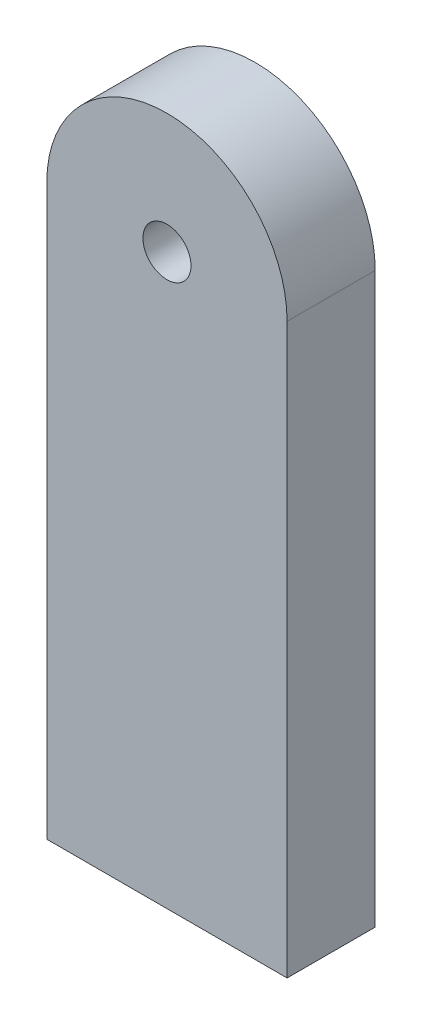
SolidWorks part; units mm, degrees
ref_plane "Front Plane" through (0, 0, 0) normal (0, 0, 1) x (1, 0, 0)
ref_plane "Top Plane" through (0, 0, 0) normal (0, 1, 0) x (1, 0, 0)
ref_plane "Right Plane" through (0, 0, 0) normal (1, 0, 0) x (0, 0, -1)
sketch "Sketch1" plane through (0, 0, 0) normal (0, 0, 1) x (1, 0, 0)
  line L0 (-3.3929, 0.0822) -> (3.3071, 0.0822)
  line L1 (-0.0429, -2.9178) -> (-0.0429, 3.0822)
  line L2 (-3.3929, -0.136) -> (-3.3929, 0.3005) construction
  line L3 (-2.4681, 0.0822) -> (-4.3177, 0.0822) construction
  line L4 (-1.9069, 2.8743) -> (-1.5289, 3.0926) construction
  line L5 (-1.2555, 2.1825) -> (-2.1803, 3.7843) construction
  line L6 (1.4431, 3.0926) -> (1.8211, 2.8743) construction
  line L7 (1.1697, 2.1825) -> (2.0945, 3.7843) construction
  line L8 (3.3071, 0.3005) -> (3.3071, -0.136) construction
  line L9 (2.3823, 0.0822) -> (4.2319, 0.0822) construction
  line L10 (1.8211, -2.7098) -> (1.4431, -2.9281) construction
  line L11 (1.1697, -2.018) -> (2.0945, -3.6198) construction
  line L12 (-1.5289, -2.9281) -> (-1.9069, -2.7098) construction
  line L13 (-1.2555, -2.018) -> (-2.1803, -3.6198) construction
  line L14 (-3.3929, 0.0822) -> (-1.7179, -2.8189)
  line L15 (-1.7179, -2.8189) -> (1.6321, -2.8189)
  line L16 (1.6321, -2.8189) -> (3.3071, 0.0822)
  line L17 (3.3071, 0.0822) -> (1.6321, 2.9834)
  line L18 (1.6321, 2.9834) -> (-1.7179, 2.9834)
  line L19 (-1.7179, 2.9834) -> (-3.3929, 0.0822)
  line L20 (7.4571, 0.0822) -> (7.4571, -35.4178)
  line L21 (7.4571, -35.4178) -> (-7.5429, -35.4178)
  line L22 (-7.5429, -35.4178) -> (-7.5429, 0.0822)
  circle A0 centre (-0.0429, 0.0822) radius 1.5
  circle A1 centre (-0.0429, 0.0822) radius 3.35 construction
  circle A2 centre (-0.0429, 0.0822) radius 7.5
  point P2 (-0.0429, 0.0822)
  point P5 (-0.0429, 0.0822)
  point P11 (-3.3929, 0.0822)
  point P14 (-3.3929, 0.0822)
  point P42 (0, 0)
  dimension "D1" = 6.7
  dimension "D3" = 15
  dimension "D4" = 35.5
  dimension "D2" = 5.8024
extrude "Boss-Extrude1" add sketch "Sketch1" along normal blind 2.5 contours A2 L19 L18 L17 L16 L15 L14 | A2 L22 L21 L20 region at (-0.0429, -7.2056, 0) region at (-0.0429, -20.5657, 0)
sketch "Sketch3" plane through (0, 0, 2.5) normal (0, 0, 1) x (1, 0, 0)
  line L0 (7.4571, 0.0822) -> (7.4571, -35.4178) construction
  line L1 (7.4571, -35.4178) -> (-7.5429, -35.4178) construction
  line L2 (-7.5429, -35.4178) -> (-7.5429, 0.0822) construction
  line L3 (7.4571, 0.0822) -> (7.4571, -35.4178)
  line L4 (7.4571, -35.4178) -> (-7.5429, -35.4178)
  line L5 (-7.5429, -35.4178) -> (-7.5429, 0.0822)
  arc A0 (7.4571, 0.0822) -> (-7.5429, 0.0822) centre (-0.0429, 0.0822) ccw construction
  arc A1 (7.4571, 0.0822) -> (-7.5429, 0.0822) centre (-0.0429, 0.0822) ccw
  circle A2 centre (-0.0429, 0.0822) radius 1.5
  dimension "D1" = 3
extrude "Boss-Extrude2" add sketch "Sketch3" along normal blind 3
